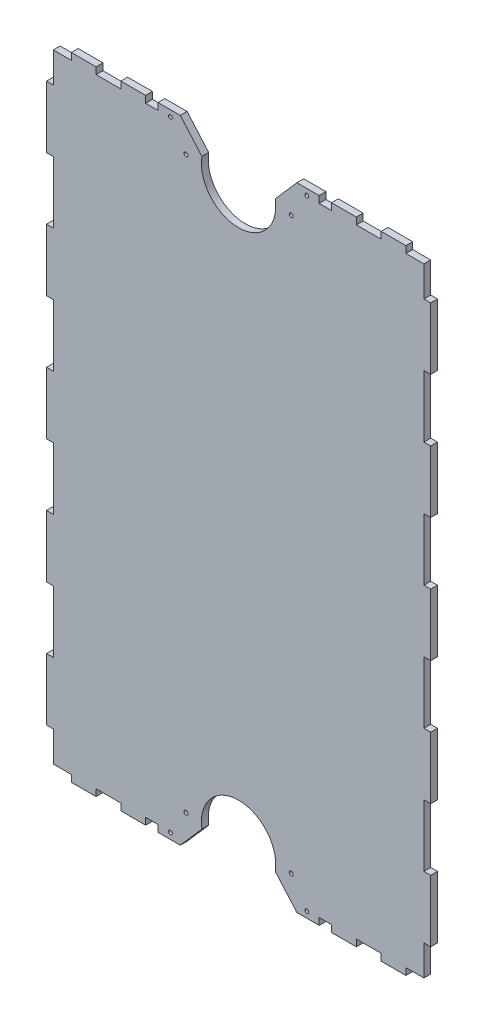
SolidWorks part; units mm, degrees
material "ﾁｰｸ材"
ref_plane "正面" through (0, 0, 0) normal (0, 0, 1) x (1, 0, 0)
ref_plane "平面" through (0, 0, 0) normal (0, 1, 0) x (1, 0, 0)
ref_plane "右側面" through (0, 0, 0) normal (1, 0, 0) x (0, 0, -1)
sketch "ｽｹｯﾁ1" plane through (0, 0, 0) normal (0, 0, 1) x (1, 0, 0)
  line L1 (155, 255) -> (-155, 255)
  line L2 (155, 255) -> (155, -255)
  line L3 (155, -255) -> (-155, -255)
  line L4 (-155, 255) -> (-155, -255)
  line L5 (155, 255) -> (-155, -255) construction
  line L6 (155, -255) -> (-155, 255) construction
  point P0 (0, 0)
  dimension "D1" = 310
  dimension "D2" = 510
extrude "ﾎﾞｽ - 押し出し1" add sketch "ｽｹｯﾁ1" along normal blind 5.5
sketch "ｽｹｯﾁ2" plane through (0, 0, 5.5) normal (0, 0, 1) x (1, 0, 0)
  line L0 (155, -255) -> (155, 255) construction
  line L1 (155, 25) -> (149.5, 25)
  line L2 (155, 25) -> (155, 75)
  line L3 (155, 75) -> (149.5, 75)
  line L4 (149.5, 25) -> (149.5, 75)
  line L9 (155, -75) -> (149.5, -75)
  line L10 (155, -75) -> (155, -25)
  line L11 (155, -25) -> (149.5, -25)
  line L12 (149.5, -75) -> (149.5, -25)
  line L13 (155, 125) -> (149.5, 125)
  line L14 (155, 125) -> (155, 175)
  line L15 (155, 175) -> (149.5, 175)
  line L16 (149.5, 125) -> (149.5, 175)
  line L17 (155, -175) -> (149.5, -175)
  line L18 (155, -175) -> (155, -125)
  line L19 (155, -125) -> (149.5, -125)
  line L20 (149.5, -175) -> (149.5, -125)
  line L21 (155, 225) -> (149.5, 225)
  line L22 (155, 225) -> (155, 275)
  line L23 (155, 275) -> (149.5, 275)
  line L24 (149.5, 225) -> (149.5, 275)
  line L25 (155, -275) -> (149.5, -275)
  line L26 (155, -275) -> (155, -225)
  line L27 (155, -225) -> (149.5, -225)
  line L28 (149.5, -275) -> (149.5, -225)
  line L29 (-149.5, 25) -> (-155, 25)
  line L30 (-149.5, 25) -> (-149.5, 75)
  line L31 (-149.5, 75) -> (-155, 75)
  line L32 (-155, 25) -> (-155, 75)
  line L33 (-149.5, -75) -> (-155, -75)
  line L34 (-149.5, -75) -> (-149.5, -25)
  line L35 (-149.5, -25) -> (-155, -25)
  line L36 (-155, -75) -> (-155, -25)
  line L37 (-149.5, 125) -> (-155, 125)
  line L38 (-149.5, 125) -> (-149.5, 175)
  line L39 (-149.5, 175) -> (-155, 175)
  line L40 (-155, 125) -> (-155, 175)
  line L41 (-149.5, -175) -> (-155, -175)
  line L42 (-149.5, -175) -> (-149.5, -125)
  line L43 (-149.5, -125) -> (-155, -125)
  line L44 (-155, -175) -> (-155, -125)
  line L45 (-149.5, 225) -> (-155, 225)
  line L46 (-149.5, 225) -> (-149.5, 275)
  line L47 (-149.5, 275) -> (-155, 275)
  line L48 (-155, 225) -> (-155, 275)
  line L49 (-149.5, -275) -> (-155, -275)
  line L50 (-149.5, -275) -> (-149.5, -225)
  line L51 (-149.5, -225) -> (-155, -225)
  line L52 (-155, -275) -> (-155, -225)
  line L53 (-155, 255) -> (-155, -255) construction
  point P53 (-152.25, 25)
  dimension "D1" = 5.5
  dimension "D2" = 50
  dimension "D3" = 25
  dimension "D4" = 50
  dimension "D5" = 50
  dimension "D6" = 50
  dimension "D7" = 50
  dimension "D8" = 50
  dimension "D9" = 5.5
  dimension "D10" = 50
  dimension "D11" = 50
  dimension "D12" = 50
  dimension "D13" = 50
  dimension "D14" = 50
  dimension "D15" = 50
  dimension "D16" = 25
extrude "ｶｯﾄ - 押し出し1" cut sketch "ｽｹｯﾁ2" against normal through all
sketch "ｽｹｯﾁ3" plane through (0, 0, 5.5) normal (0, 0, 1) x (1, 0, 0)
  line L0 (47.0333, 255) -> (29.5804, 235)
  line L2 (149.5, 255) -> (-149.5, 255) construction
  line L3 (47.0333, 255) -> (-47.0333, 255)
  line L4 (-47.0333, 255) -> (-29.5804, 235)
  line L5 (0, 0) -> (-89.4663, 0) construction
  line L6 (-47.0333, -255) -> (-29.5804, -235)
  line L7 (47.0333, -255) -> (-47.0333, -255)
  line L8 (47.0333, -255) -> (29.5804, -235)
  arc A1 (29.5804, 235) -> (-29.5804, 235) centre (0, 230) cw
  arc A2 (29.5804, -235) -> (-29.5804, -235) centre (0, -230) ccw
  dimension "D1" = 30
  dimension "D2" = 25
  dimension "D3" = 19
  dimension "D4" = 19
  dimension "D5" = 5
  dimension "D6" = 5
extrude "ｶｯﾄ - 押し出し2" cut sketch "ｽｹｯﾁ3" against normal through all
sketch "ｽｹｯﾁ5" plane through (0, 0, 5.5) normal (0, 0, 1) x (1, 0, 0)
  line L0 (0, 0) -> (-26.2638, 0) construction
  circle A0 centre (-42.5, 230) radius 1.6
  circle A1 centre (42.5, 230) radius 1.6
  circle A2 centre (42.5, -230) radius 1.6
  circle A3 centre (-42.5, -230) radius 1.6
  point P4 (0, 230)
  point P13 (0, -230)
  dimension "D1" = 3.2
  dimension "D2" = 42.5
  dimension "D3" = 42.5
extrude "ｶｯﾄ - 押し出し3" cut sketch "ｽｹｯﾁ5" against normal through all
sketch "ｽｹｯﾁ6" plane through (0, 0, 5.5) normal (0, 0, 1) x (1, 0, 0)
  line L0 (149.5, 255) -> (47.0333, 255) construction
  line L1 (0, 0) -> (-34.0565, 0) construction
  circle A0 centre (55, 250) radius 1.55
  circle A1 centre (-55, 250) radius 1.55
  circle A2 centre (-55, -250) radius 1.55
  circle A3 centre (55, -250) radius 1.55
  dimension "D1" = 3.1
  dimension "D3" = 5
  dimension "D2" = 55
  dimension "D4" = 55
extrude "ｶｯﾄ - 押し出し4" cut sketch "ｽｹｯﾁ6" against normal through all
sketch "ｽｹｯﾁ7" plane through (0, 0, 5.5) normal (0, 0, 1) x (1, 0, 0)
  line L0 (149.5, 255) -> (47.0333, 255) construction
  line L1 (135, 255) -> (155, 255)
  line L2 (135, 255) -> (135, 249.5)
  line L3 (135, 249.5) -> (155, 249.5)
  line L4 (155, 255) -> (155, 249.5)
  line L5 (155, 175) -> (155, 225) construction
  line L6 (95, 255) -> (95, 249.5)
  line L7 (95, 255) -> (115, 255)
  line L8 (115, 255) -> (115, 249.5)
  line L9 (95, 249.5) -> (115, 249.5)
  line L10 (0, 0) -> (0, 80.2112) construction
  line L11 (75, 255) -> (65, 255)
  line L12 (75, 255) -> (75, 249.5)
  line L13 (75, 249.5) -> (65, 249.5)
  line L14 (65, 255) -> (65, 249.5)
  line L15 (0, 0) -> (-49.6238, 0) construction
  line L16 (-75, 249.5) -> (-65, 249.5)
  line L17 (-65, 255) -> (-65, 249.5)
  line L18 (-75, 255) -> (-65, 255)
  line L19 (-75, 255) -> (-75, 249.5)
  line L20 (-95, 255) -> (-115, 255)
  line L21 (-115, 255) -> (-115, 249.5)
  line L22 (-95, 249.5) -> (-115, 249.5)
  line L23 (-95, 255) -> (-95, 249.5)
  line L24 (-135, 249.5) -> (-155, 249.5)
  line L25 (-155, 255) -> (-155, 249.5)
  line L26 (-135, 255) -> (-155, 255)
  line L27 (-135, 255) -> (-135, 249.5)
  line L28 (-135, -255) -> (-135, -249.5)
  line L29 (-135, -255) -> (-155, -255)
  line L30 (-155, -255) -> (-155, -249.5)
  line L31 (-135, -249.5) -> (-155, -249.5)
  line L32 (-95, -255) -> (-95, -249.5)
  line L33 (-95, -249.5) -> (-115, -249.5)
  line L34 (-115, -255) -> (-115, -249.5)
  line L35 (-95, -255) -> (-115, -255)
  line L36 (-75, -255) -> (-75, -249.5)
  line L37 (-75, -255) -> (-65, -255)
  line L38 (-65, -255) -> (-65, -249.5)
  line L39 (-75, -249.5) -> (-65, -249.5)
  line L40 (75, -249.5) -> (65, -249.5)
  line L41 (65, -255) -> (65, -249.5)
  line L42 (75, -255) -> (65, -255)
  line L43 (75, -255) -> (75, -249.5)
  line L44 (95, -255) -> (115, -255)
  line L45 (115, -255) -> (115, -249.5)
  line L46 (95, -249.5) -> (115, -249.5)
  line L47 (95, -255) -> (95, -249.5)
  line L48 (135, -249.5) -> (155, -249.5)
  line L49 (155, -255) -> (155, -249.5)
  line L50 (135, -255) -> (155, -255)
  line L51 (135, -255) -> (135, -249.5)
  point P16 (75, 252.25)
  point P17 (115, 252.25)
  dimension "D1" = 5.5
  dimension "D2" = 20
  dimension "D4" = 10
  dimension "D5" = 20
  dimension "D6" = 20
  dimension "D3" = 2
extrude "ｶｯﾄ - 押し出し5" cut sketch "ｽｹｯﾁ7" against normal through all
